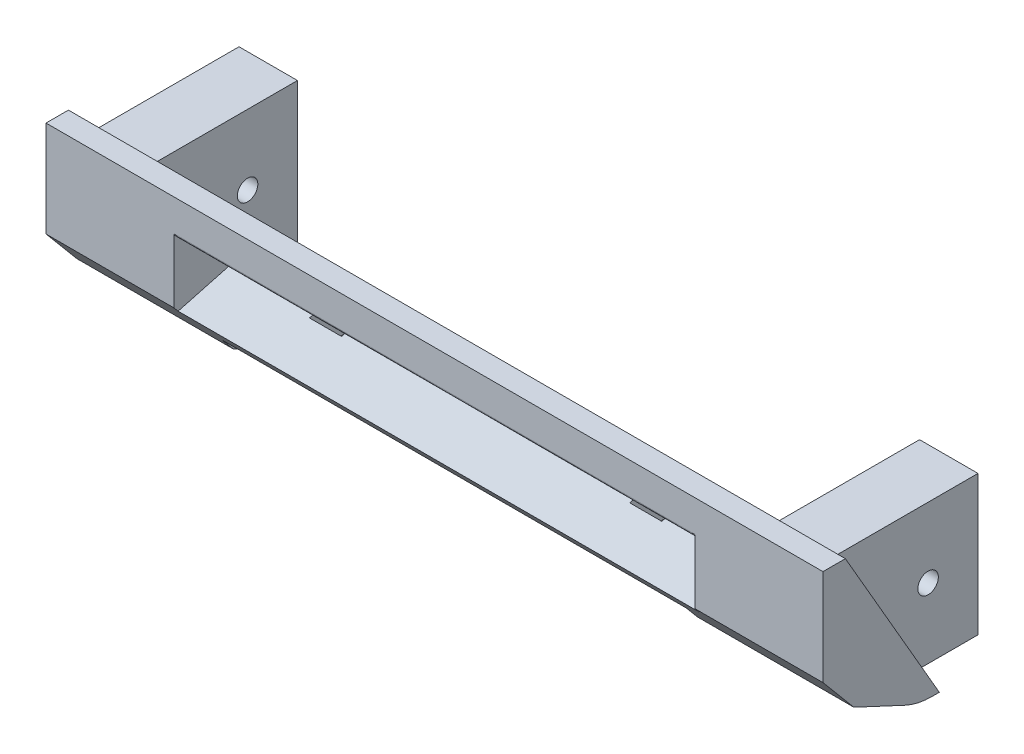
SolidWorks part; units mm, degrees
ref_plane "Front Plane" through (0, 0, 0) normal (0, 0, 1) x (1, 0, 0)
ref_plane "Top Plane" through (0, 0, 0) normal (0, 1, 0) x (1, 0, 0)
ref_plane "Right Plane" through (0, 0, 0) normal (1, 0, 0) x (0, 0, -1)
sketch "Sketch1" plane through (0, 0, 0) normal (1, 0, 0) x (0, 0, -1)
  line L0 (0, 0) -> (-29.3294, 50.8)
  line L1 (0, 0) -> (50, 0) construction
  line L2 (-29.3294, 50.8) -> (-36.3294, 50.8)
  line L3 (-36.3294, 13.8) -> (-6.7352, 0)
  line L6 (-36.3294, 50.8) -> (-36.3294, 13.8)
  line L7 (-6.7352, 0) -> (0, 0)
  line L8 (0, 0) -> (0, 21.8413) construction
  dimension "D1" = 65
  dimension "D2" = 6.7352
  dimension "D3" = 37
extrude "Boss-Extrude2" add sketch "Sketch1" along normal mid plane 242.55
sketch "Sketch2" plane through (0, 0, 0) normal (0, 0, 1) x (1, 0, 0)
  line L0 (0, 0) -> (0, 50.8) construction
  line L5 (115.75, 47.625) -> (96.7, 47.625) construction
  line L6 (115.75, 47.625) -> (115.75, 3.175) construction
  line L11 (115.75, 3.175) -> (96.7, 3.175) construction
  line L12 (96.7, 47.625) -> (96.7, 3.175) construction
  line L14 (115.35, 47.225) -> (115.35, 3.575)
  line L15 (115.35, 3.575) -> (97.1, 3.575)
  line L21 (119.775, 0) -> (-119.6, 0) construction
  line L28 (97.1, 47.225) -> (97.1, 3.575)
  line L29 (115.35, 47.225) -> (97.1, 47.225)
  line L30 (-96.7, 47.625) -> (-96.7, 3.175) construction
  line L31 (-115.75, 3.175) -> (-96.7, 3.175) construction
  line L32 (-115.75, 47.625) -> (-115.75, 3.175) construction
  line L33 (-115.75, 47.625) -> (-96.7, 47.625) construction
  line L34 (-115.35, 47.225) -> (-97.1, 47.225)
  line L35 (-97.1, 47.225) -> (-97.1, 3.575)
  line L36 (-115.35, 3.575) -> (-97.1, 3.575)
  line L37 (-115.35, 47.225) -> (-115.35, 3.575)
  line L40 (119.775, 50.8) -> (-119.775, 50.8) construction
  line L41 (119.775, 0) -> (119.775, 50.8) construction
  dimension "D2" = 19.05
  dimension "D4" = 3.175
  dimension "D7" = 4.025
  dimension "D1" = 193.4
  dimension "D3" = 3.175
  dimension "D5" = 0.4
extrude "Boss-Extrude1" add sketch "Sketch2" along normal up to surface and the other way blind 18 up to face at (0, 25.4, 14.6647)
sketch "Sketch12" plane through (0, -2.5797, 1.2029) normal (0, -0.9063, 0.4226) x (1, 0, 0)
  line L0 (-95.2, -603.0139) -> (-95.2, 0.9459) construction
  line L1 (-95.2, -603.0139) -> (-95.2, 0.9459) construction
  line L2 (119.775, 0) -> (-119.775, 0) construction
  line L3 (70, 15) -> (-70, 15)
  line L4 (70, 15) -> (70, 0)
  line L5 (70, 0) -> (-70, 0)
  line L6 (-70, 15) -> (-70, 0)
  line L7 (70, 15) -> (-70, 0) construction
  line L8 (70, 0) -> (-70, 15) construction
  line L10 (95.2, 44.3946) -> (-95.2, 44.3946)
  line L11 (95.2, 44.3946) -> (95.2, 19.3946)
  line L12 (95.2, 19.3946) -> (-95.2, 19.3946)
  line L13 (-95.2, 44.3946) -> (-95.2, 19.3946)
  line L14 (95.2, 44.3946) -> (-95.2, 19.3946) construction
  line L15 (95.2, 19.3946) -> (-95.2, 44.3946) construction
  line L16 (-120.6, 54.3946) -> (120.6, 54.3946) construction
  point P2 (0, 7.5)
  point P11 (0, 31.8946)
  dimension "D1" = 15
  dimension "D2" = 140
  dimension "D3" = 10
  dimension "D4" = 25
  dimension "D5" = 4.3946
extrude "Cut-Extrude4" [suppressed] cut sketch "Sketch12" against normal up to next
hole_wizard "M6 Clearance Hole1" positions "Sketch11" profile "Sketch10" hole size "M6" standard "ANSI Metric" end condition through all
sketch "Sketch11" plane through (115.35, 0, 0) normal (1, 0, 0) x (0, 0, -1)
  point P0 (2.4206, 25.4)
sketch "Sketch10" plane through (115.35, 25.4, -2.4206) normal (0, 1, 0) x (0, 0, -1)
  line L0 (0, 0) -> (0, 236.625)
  line L1 (0, 236.625) -> (3.2, 236.625)
  line L2 (3.2, 236.625) -> (3.2, 0)
  line L5 (3.2, 0) -> (0, 0)
  line L11 (0, -6.35) -> (0, 107.95) construction
  dimension "Thru Hole Dia." = 6.4
  dimension "Thru Hole Depth" = 236.625
sketch "Sketch13" plane through (0, 0, 0) normal (0, 0, 1) x (1, 0, 0)
  line L0 (121.275, 0) -> (-121.275, 0) construction
  line L1 (-72.5, 13.5) -> (72.5, 13.5)
  line L2 (-72.5, 13.5) -> (-72.5, 0)
  line L3 (-72.5, 0) -> (72.5, 0)
  line L4 (72.5, 13.5) -> (72.5, 0)
  line L5 (-72.5, 13.5) -> (72.5, 0) construction
  line L6 (-72.5, 0) -> (72.5, 13.5) construction
  line L7 (121.275, 50.8) -> (-121.275, 50.8) construction
  line L8 (-81.275, 23.8) -> (81.275, 23.8)
  line L9 (-81.275, 23.8) -> (-81.275, 37.8)
  line L10 (-81.275, 37.8) -> (81.275, 37.8)
  line L11 (81.275, 23.8) -> (81.275, 37.8)
  line L12 (-81.275, 23.8) -> (81.275, 37.8) construction
  line L13 (-81.275, 37.8) -> (81.275, 23.8) construction
  line L14 (-121.275, 50.8) -> (-121.275, 13.8) construction
  line L15 (0, 50.8) -> (0, -69.7748) construction
  point P0 (0, 6.75)
  point P7 (0, 30.8)
  dimension "D1" = 13.5
  dimension "D2" = 13
  dimension "D3" = 40
  dimension "D4" = 14
  dimension "D5" = 145
extrude "Cut-Extrude6" cut sketch "Sketch13" against normal through all both and the other way through all
chamfer "Chamfer5" distance 18 angle 15 1 edges at (0, 37.8, 21.8238) first distance on face at (0, 37.8, 29.0766)
chamfer "Chamfer6" distance 18 angle 15 1 edges at (0, 23.8, 36.3294) first distance on face at (0, 23.8, 25.0352)
chamfer "Chamfer7" distance 7 angle 40 1 edges at (0, 13.8, 36.3294) first distance on face at (0, 28.8566, 36.3294)
sketch "Sketch14" plane through (0, 13.5, 0) normal (0, -1, 0) x (1, 0, 0)
  line L0 (-50, 11.7942) -> (50, 11.7942) construction
  line L1 (72.5, 7.7942) -> (-72.5, 7.7942) construction
  line L2 (46.5, 15.7942) -> (53.5, 15.7942)
  line L3 (46.5, 15.7942) -> (46.5, 7.7942)
  line L4 (46.5, 7.7942) -> (53.5, 7.7942)
  line L5 (53.5, 15.7942) -> (53.5, 7.7942)
  line L6 (46.5, 15.7942) -> (53.5, 7.7942) construction
  line L7 (46.5, 7.7942) -> (53.5, 15.7942) construction
  line L9 (-53.5, 15.7942) -> (-46.5, 15.7942)
  line L10 (-53.5, 15.7942) -> (-53.5, 7.7942)
  line L11 (-53.5, 7.7942) -> (-46.5, 7.7942)
  line L12 (-46.5, 15.7942) -> (-46.5, 7.7942)
  line L13 (-53.5, 15.7942) -> (-46.5, 7.7942) construction
  line L14 (-53.5, 7.7942) -> (-46.5, 15.7942) construction
  point P0 (50, 11.7942)
  point P3 (0, 11.7942)
  dimension "D1" = 7
  dimension "D2" = 7
  dimension "D3" = 8
  dimension "D4" = 100
ref_plane "Plane2" through (0, 13.5, 7.7942) normal (0, 0.866, 0.5) x (-1, 0, 0)
sketch "Sketch15" plane through (0, 13.5, 7.7942) normal (0, 0.866, 0.5) x (-1, 0, 0)
  line L0 (-50, 3) -> (50, 3) construction
  line L1 (-72.5, 0) -> (72.5, 0) construction
  line L2 (-45, 6) -> (-55, 6)
  line L3 (-45, 6) -> (-45, 0)
  line L4 (-45, 0) -> (-55, 0)
  line L5 (-55, 6) -> (-55, 0)
  line L6 (-45, 6) -> (-55, 0) construction
  line L7 (-45, 0) -> (-55, 6) construction
  line L9 (45, 6) -> (55, 6)
  line L10 (45, 6) -> (45, 0)
  line L11 (45, 0) -> (55, 0)
  line L12 (55, 6) -> (55, 0)
  line L13 (45, 6) -> (55, 0) construction
  line L14 (45, 0) -> (55, 6) construction
  point P3 (0, 3)
  dimension "D1" = 10
  dimension "D2" = 10
  dimension "D3" = 6
  dimension "D4" = 100
extrude "Cut-Extrude8" cut sketch "Sketch15" along normal up to surface (14.7306 mm away) up to face at (0, 21.5558, 26.7049)
fillet "Fillet1" radius 4 1 edges at (0, 38.7363, 36.3294) second distance 1 first distance on face at (0, 40.3566, 30.2824)
fillet "Fillet2" radius 20 2 edges at (-96.8875, 0, 6.7352) (96.8875, 0, 6.7352)
equation "\"D1@Sketch2\"=187.05mm+0.25in"
equation "\"RailSpacing\" = 191.75mm"
equation "\"D1@Boss-Extrude2\"=\"RailSpacing\"+2in"
